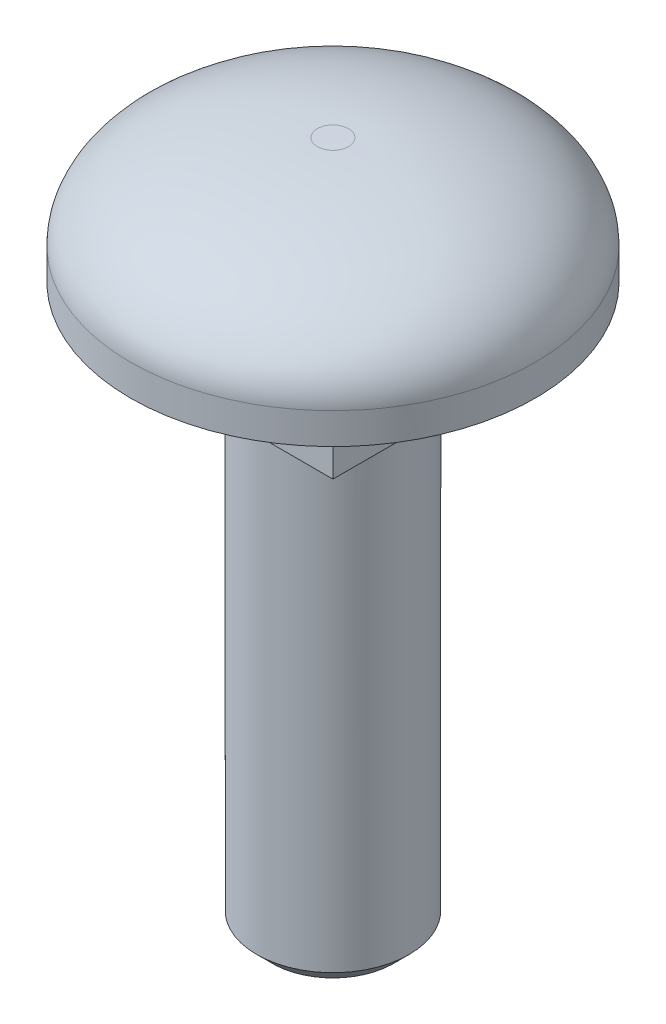
SolidWorks part; units mm, degrees
ref_plane "Front Plane" through (0, 0, 0) normal (0, 0, 1) x (1, 0, 0)
ref_plane "Top Plane" through (0, 0, 0) normal (0, 1, 0) x (1, 0, 0)
ref_plane "Right Plane" through (0, 0, 0) normal (1, 0, 0) x (0, 0, -1)
sketch "Sketch1" plane through (0, 0, 0) normal (1, 0, 0) x (0, 0, -1)
  line L0 (0, 0) -> (0, -20) construction
  line L1 (-6.5, -2) -> (6.5, -2)
  line L2 (-6.5, -2) -> (-6.5, 2)
  line L3 (-6.5, 2) -> (6.5, 2)
  line L4 (6.5, -2) -> (6.5, 2)
  line L5 (-6.5, -2) -> (6.5, 2) construction
  line L6 (-6.5, 2) -> (6.5, -2) construction
  line L7 (0, 2) -> (0, -20)
  line L8 (-2.45, -20) -> (2.45, -20)
  line L9 (-2.45, -20) -> (-2.45, -2)
  line L10 (-2.45, -2) -> (2.45, -2)
  line L11 (2.45, -20) -> (2.45, -2)
  line L12 (-2.45, -20) -> (2.45, -2) construction
  line L13 (-2.45, -2) -> (2.45, -20) construction
  point P0 (0, 0)
  point P8 (0, -11)
  dimension "D1" = 13
  dimension "D2" = 4
  dimension "D3" = 4.9
  dimension "D4" = 18
revolve "Revolve1" add sketch "Sketch1" angle 360 about L7 region at (0, 0, 3.25) region at (0, -11, 1.225)
fillet "Fillet1" radius 6 1 edges at (0, 2, 6.5) second distance 3 first distance on face at (0, 2, 6.5)
sketch "Sketch2" plane through (0, -2, 0) normal (0, -1, 0) x (1, 0, 0)
  line L1 (-2.5, -2.5) -> (2.5, -2.5)
  line L2 (-2.5, -2.5) -> (-2.5, 2.5)
  line L3 (-2.5, 2.5) -> (2.5, 2.5)
  line L4 (2.5, -2.5) -> (2.5, 2.5)
  line L5 (-2.5, -2.5) -> (2.5, 2.5) construction
  line L6 (-2.5, 2.5) -> (2.5, -2.5) construction
  point P0 (0, 0)
  point P6 (0, 0)
  dimension "D1" = 5
  dimension "D2" = 5
extrude "Boss-Extrude1" add sketch "Sketch2" along normal blind 3
chamfer "Chamfer1" distance 0.5 angle 45 1 edges at (0, -20, 2.45)
